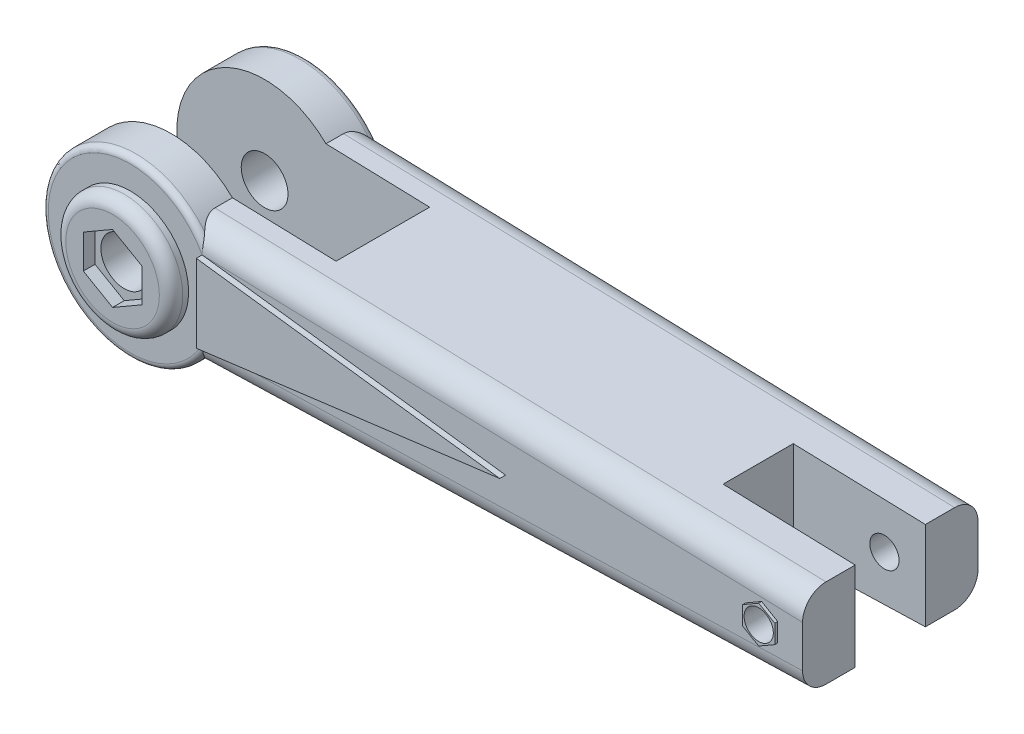
SolidWorks part; units mm, degrees
ref_plane "Front Plane" through (0, 0, 0) normal (0, 0, 1) x (1, 0, 0)
ref_plane "Top Plane" through (0, 0, 0) normal (0, 1, 0) x (1, 0, 0)
ref_plane "Right Plane" through (0, 0, 0) normal (1, 0, 0) x (0, 0, -1)
sketch "Sketch1" plane through (0, 0, 0) normal (0, 0, 1) x (1, 0, 0)
  line L0 (0, 0) -> (-120, 0) construction
  line L1 (-10.4977, 10.7144) -> (-10.4977, -10.7144) construction
  line L2 (-115, -7.5826) -> (-115, 7.5826) construction
  line L3 (-10.4977, 10.7144) -> (-115, 7.5826)
  line L4 (-10.4977, -10.7144) -> (-115, -7.5826)
  line L5 (-115, 7.5826) -> (-115, -7.5826)
  arc A0 (-10.4977, -10.7144) -> (-10.4977, 10.7144) centre (0, 0) ccw
  dimension "D1" = 30
  dimension "D2" = 120
  dimension "D4" = 10.4977
  dimension "D5" = 115
extrude "Boss-Extrude2" add sketch "Sketch1" along normal mid plane 30
sketch "Sketch2" plane through (0, 0, 0) normal (0, 0, 1) x (1, 0, 0)
  circle A0 centre (0, 0) radius 30
  dimension "D1" = 60
extrude "Cut-Extrude1" cut sketch "Sketch2" against normal mid plane 16
sketch "Sketch3" plane through (0, 0, 15) normal (0, 0, 1) x (1, 0, 0)
  circle A0 centre (0, 0) radius 4
  dimension "D1" = 8
extrude "Cut-Extrude3" cut sketch "Sketch3" against normal through all
sketch "Sketch4" plane through (-115, 0, 0) normal (-1, 0, 0) x (0, 0, 1)
  circle A0 centre (0, 0) radius 5
  dimension "D1" = 10
fillet "Fillet1" radius 4 4 edges at (-62.7488, -9.1485, -15) (-62.7488, 9.1485, -15) (-62.7488, -9.1485, 15) (-62.7488, 9.1485, 15)
sketch "Sketch6" plane through (0, 0, 15) normal (0, 0, 1) x (1, 0, 0)
  circle A0 centre (0, 0) radius 10
  dimension "D1" = 20
extrude "Boss-Extrude4" add sketch "Sketch6" along normal blind 3
fillet "Fillet2" radius 2 1 edges at (10, 0, 18)
sketch "Sketch7" plane through (0, 0, 18) normal (0, 0, 1) x (1, 0, 0)
  circle A0 centre (0, 0) radius 4 construction
  circle A1 centre (0, 0) radius 4
extrude "Cut-Extrude5" cut sketch "Sketch7" against normal through all
sketch "Sketch8" plane through (0, 0, -15) normal (0, 0, -1) x (-1, 0, 0)
  circle A0 centre (0, 0) radius 10
  dimension "D1" = 20
extrude "Boss-Extrude5" add sketch "Sketch8" along normal blind 3
fillet "Fillet3" radius 2 1 edges at (-10, 0, -18)
sketch3d "3DSketch1"
  circle A0 centre (0, 0, -15) radius 4 construction
  circle A1 centre (0, 0, -15) radius 4
  point P2 (0, 0, -11)
  point P4 (0, 0, -11)
sketch "Sketch10" plane through (0, 0, 15) normal (0, 0, 1) x (1, 0, 0)
  circle A0 centre (0, 0) radius 4
  dimension "D1" = 8
extrude "Cut-Extrude6" cut sketch "Sketch10" against normal through all
sketch "Sketch11" plane through (0, 0, 18) normal (0, 0, 1) x (1, 0, 0)
  line L1 (0, 5.7735) -> (-5, 2.8868)
  line L2 (-5, 2.8868) -> (-5, -2.8868)
  line L3 (-5, -2.8868) -> (0, -5.7735)
  line L4 (0, -5.7735) -> (5, -2.8868)
  line L5 (5, -2.8868) -> (5, 2.8868)
  line L6 (5, 2.8868) -> (0, 5.7735)
  circle A0 centre (0, 0) radius 5 construction
  dimension "D1" = 10
extrude "Cut-Extrude7" cut sketch "Sketch11" against normal blind 2
mirror "Mirror3" about plane through (0, 0, 0) normal (0, 0, 1) of "Cut-Extrude6", "Cut-Extrude7"
fillet "Fillet4" radius 1 2 edges at (15, 0, -15) (15, 0, 15)
sketch "Sketch12" plane through (0, 0, 15) normal (0, 0, 1) x (1, 0, 0)
  line L0 (-12.3154, 6.6582) -> (-12.3154, -6.6582)
  line L1 (-12.3154, -6.6582) -> (-64.2144, 0)
  line L2 (-64.2144, 0) -> (-12.3154, 6.6582)
extrude "Boss-Extrude6" add sketch "Sketch12" along normal blind 1
mirror "Mirror4" about plane through (0, 0, 0) normal (0, 0, 1) of "Boss-Extrude6"
sketch "Sketch13" plane through (0, 0, 0) normal (0, 0, 1) x (1, 0, 0)
  line L0 (-115, 11.9565) -> (-92.4094, 11.9565)
  line L1 (-115, 5) -> (-115, -5) construction
  line L2 (-92.4094, 11.9565) -> (-92.4094, -9.3709)
  line L3 (-92.4094, -9.3709) -> (-115, -9.3709)
  line L4 (-115, -9.3709) -> (-115, 11.9565)
  point P5 (-115, 3.5808)
  point P7 (-115, -3.5808)
extrude "Cut-Extrude8" cut sketch "Sketch13" against normal mid plane 12
sketch "Sketch14" plane through (0, 0, 15) normal (0, 0, 1) x (1, 0, 0)
  line L0 (-115, 3.5808) -> (-115, -3.5808) construction
  circle A0 centre (-108, 0) radius 2.5
  dimension "D1" = 5
  dimension "D2" = 7
extrude "Cut-Extrude9" cut sketch "Sketch14" against normal through all
sketch "Sketch15" plane through (0, 0, 15) normal (0, 0, 1) x (1, 0, 0)
  line L1 (-110.75, 1.5877) -> (-110.75, -1.5877)
  line L2 (-110.75, -1.5877) -> (-108, -3.1754)
  line L3 (-108, -3.1754) -> (-105.25, -1.5877)
  line L4 (-105.25, -1.5877) -> (-105.25, 1.5877)
  line L5 (-105.25, 1.5877) -> (-108, 3.1754)
  line L6 (-108, 3.1754) -> (-110.75, 1.5877)
  circle A0 centre (-108, 0) radius 2.75 construction
  circle A1 centre (-108, 0) radius 2.5 construction
  circle A2 centre (-108, 0) radius 2.5
  dimension "D1" = 5.5
extrude "Boss-Extrude7" add sketch "Sketch15" along normal blind 0.5 contours A2 | L1 L2 L3 L4 L5 L6
mirror "Mirror5" about plane through (0, 0, 0) normal (0, 0, 1) of "Cut-Extrude9", "Boss-Extrude7"
sketch "Sketch17" plane through (0, 0, 15) normal (0, 0, 1) x (1, 0, 0)
  point P1 (0, 0)
sketch "Sketch21" plane through (0, 0, 15) normal (0, 0, 1) x (1, 0, 0)
  point P1 (0, 0)
sketch "Sketch22" plane through (0, 0, 0) normal (0, 0, 1) x (1, 0, 0)
  point P0 (-108, 0)
move or copy body "Body-Move/Copy1" bodies to move or copy 121 copy no translate (108, 0, 0)
sketch "Sketch24" plane through (0, 0, 0) normal (0, 0, 1) x (1, 0, 0)
  line L0 (0, 0) -> (108, 0) construction
move or copy body "Body-Move/Copy2" bodies to move or copy 122 copy no rotation origin (0, 0, 0) rotation axis (0, 1, 0) rotation angle 180
